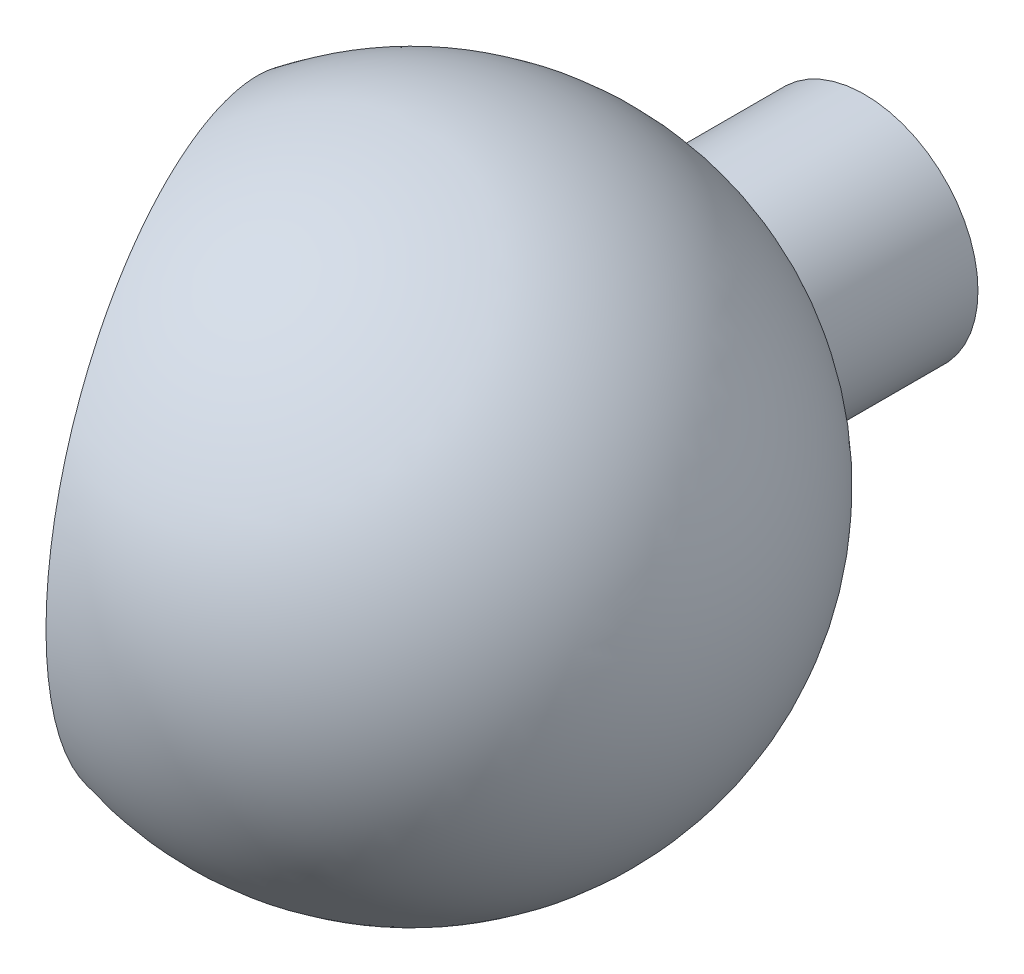
SolidWorks part; units mm, degrees
ref_plane "Plan de face" through (0, 0, 0) normal (0, 0, 1) x (1, 0, 0)
ref_plane "Plan de dessus" through (0, 0, 0) normal (0, 1, 0) x (1, 0, 0)
ref_plane "Plan de droite" through (0, 0, 0) normal (1, 0, 0) x (0, 0, -1)
sketch "Esquisse1" plane through (0, 0, 0) normal (0, 0, 1) x (1, 0, 0)
  circle A0 centre (0, 0) radius 2
  dimension "D1" = 4
extrude "Boss.-Extru.1" add sketch "Esquisse1" along normal blind 5
ref_plane "Plan1" through (0, 0, 8) normal (0, 0, -1) x (-1, 0, 0)
sketch "Esquisse3" plane through (0, 0, 8) normal (0, 0, -1) x (-1, 0, 0)
  line L0 (0, 5.5) -> (0, -5.5) construction
  line L1 (0, 5.5) -> (0, -5.5)
  arc A0 (0, 5.5) -> (0, -5.5) centre (0, 0) ccw
  dimension "D1" = 11
revolve "Révolution1" add sketch "Esquisse3" angle 360 about L0
sketch "Esquisse4" plane through (0, 0, 8) normal (0, 0, -1) x (-1, 0, 0)
  line L0 (0, 20.2126) -> (0, -30.2649) construction
ref_plane "Plan2" through (2.5712, 0, 0.9358) normal (-0.9397, 0, -0.342) x (0, -1, 0)
sketch "Esquisse5" plane through (0, 0, 0) normal (0, 1, 0) x (1, 0, 0)
  line L0 (-3.8549, -5.6785) -> (-1.4608, -12.2563)
  line L1 (0, 8.3663) -> (0, -21.8663) construction
  line L2 (-3.8549, -5.6785) -> (-4.2712, -4.5349)
  line L3 (-1.4608, -12.2563) -> (-1.0445, -13.3999)
  line L4 (-4.2712, -4.5349) -> (-11.8735, -7.3019)
  line L5 (-11.8735, -7.3019) -> (-8.6469, -16.1669)
  line L6 (-8.6469, -16.1669) -> (-1.0445, -13.3999)
  circle A0 centre (0, -8) radius 4.5 construction
  arc A1 (-2, -2.8765) -> (2, -2.8765) centre (0, -8) ccw construction
  point P10 (0, 0)
  dimension "D1" = 9
  dimension "D2" = 7
  dimension "D3" = 20
extrude "Enlèv. mat.-Extru.1" cut sketch "Esquisse5" against normal blind 10 and the other way blind 10
sketch "Esquisse6" plane through (0, 0, 8) normal (0, 0, -1) x (-1, 0, 0)
  line L0 (-4.5, 0) -> (4.5, 0)
  arc A0 (4.5, 0) -> (-4.5, 0) centre (0, 0) ccw
  dimension "D1" = 9
revolve "Enlèvement de matière-Révolution2" cut sketch "Esquisse6" angle 360 about L0
